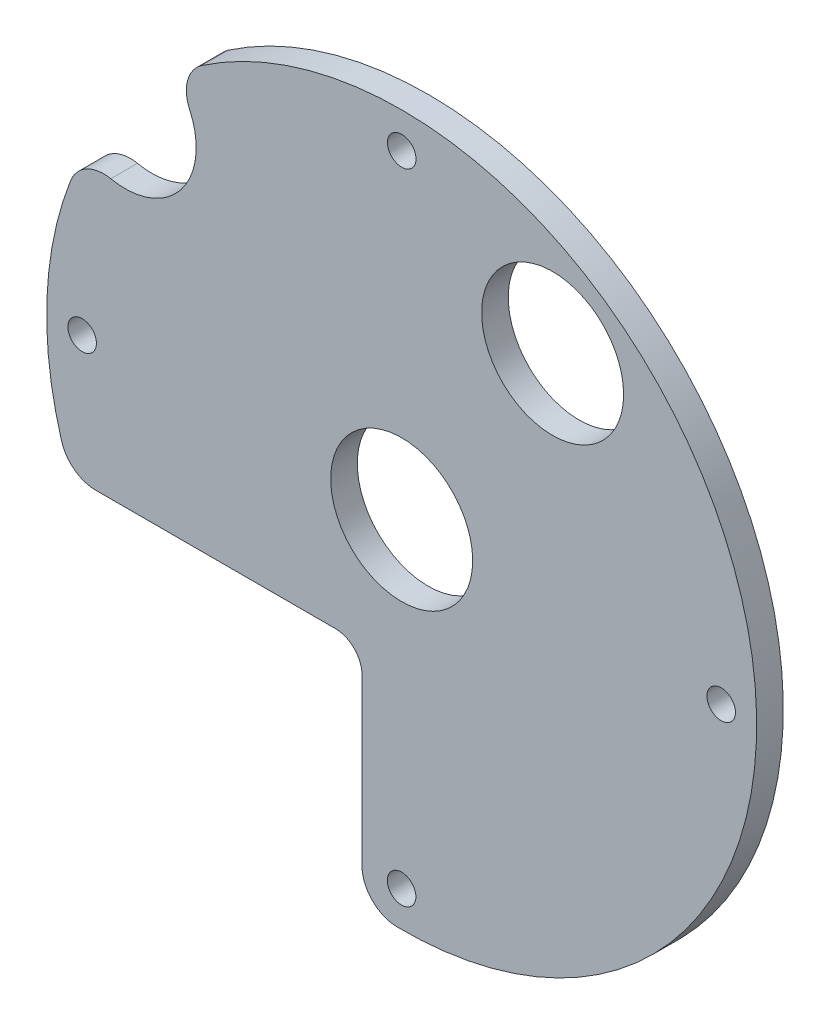
SolidWorks part; units mm, degrees
material "PET"
ref_plane "Front Plane" through (0, 0, 0) normal (0, 0, 1) x (1, 0, 0)
ref_plane "Top Plane" through (0, 0, 0) normal (0, 1, 0) x (1, 0, 0)
ref_plane "Right Plane" through (0, 0, 0) normal (1, 0, 0) x (0, 0, -1)
sketch "LayoutSke"
sketch_block_instance "Gearing 2.0-1"
sketch_block "Gearing 2.0" parameters "D5"=76.2, "D6"=25.4, "D7"=101.6, "D8"=19.05, "D1"=228.6, "D2"=123.2, "D3"=85.227, "D4"=76.454, "D9"=39.0329, "D10"=76.454, "D11"=47.625, "D12"=63.5
sketch "Sketch2" plane through (0, 0, 0) normal (0, 0, 1) x (1, 0, 0)
  line L1 (-114.3, 123.2) -> (114.3, 123.2)
  line L2 (-114.3, 123.2) -> (-114.3, -41.9)
  line L3 (-114.3, -41.9) -> (114.3, -41.9)
  line L4 (114.3, 123.2) -> (114.3, -41.9)
  dimension "D1" = 165.1
extrude "Boss-Extrude1" add sketch "Sketch2" along normal blind 4.7625
hole_wizard "1/2 (0.5) Diameter Hole1" positions "Sketch3" profile "Sketch4" hole size "1/2" standard "ANSI Inch" end condition through all
sketch "Sketch3" plane through (0, 0, 4.7625) normal (0, 0, 1) x (1, 0, 0)
  line L0 (114.3, 123.2) -> (-114.3, 123.2) construction
  point P0 (-38.227, 85.227)
  point P3 (38.227, 85.227)
  point P7 (11.2268, 45.984)
  dimension "D1" = 77.216
  dimension "D2" = 27.0002
sketch "Sketch4" plane through (-38.227, 85.227, 4.7625) normal (1, 0, 0) x (0, -1, 0)
  line L0 (0, 0) -> (0, 4.7625)
  line L1 (0, 4.7625) -> (12.7, 4.7625)
  line L2 (12.7, 4.7625) -> (12.7, 0)
  line L5 (12.7, 0) -> (0, 0)
  line L11 (0, -6.35) -> (0, 107.95) construction
  dimension "Thru Hole Dia." = 25.4
  dimension "Thru Hole Depth" = 4.7625
ref_axis "MotorShaft" through (-24.7438, -6.3341, 0) along (0, 0, 1)
ref_axis "IntermediateShaft" through (11.2395, 45.9865, 0) along (0, 0, 1)
sketch "Sketch5" plane through (0, 0, 4.7625) normal (0, 0, 1) x (1, 0, 0)
  line L0 (11.2395, 45.9865) -> (38.227, 85.227) construction
  line L10 (29.0606, 96.2614) -> (22.9081, 78.9046)
  line L11 (37.8038, 68.6601) -> (51.8105, 80.6153)
  line L12 (11.2395, 45.9865) -> (11.2395, -7.3535) construction
  arc A2 (29.0606, 96.2614) -> (51.8105, 80.6153) centre (11.2395, 45.9865) ccw
  circle A3 centre (11.2395, 45.9865) radius 50.8 construction
  arc A5 (37.8038, 68.6601) -> (22.9081, 78.9046) centre (11.2395, 45.9865) ccw
  dimension "D1" = 2.54
  dimension "D2" = 69.85
  dimension "D3" = 15
  dimension "D4" = 15
sketch "Sketch7" plane through (0, 0, 0) normal (0, 0, -1) x (-1, 0, 0)
  line L0 (-114.3, 123.2) -> (114.3, 123.2) construction
  line L1 (38.227, 85.227) -> (-38.227, 85.227) construction
  circle A0 centre (0, 180.35) radius 66.675
  point P4 (0, 123.2)
  point P6 (0, 113.675)
  dimension "D1" = 133.35
  dimension "D2" = 9.525
  dimension "D3" = 95.123
extrude "Cut-Extrude4" cut sketch "Sketch7" against normal through all
fillet "Fillet1" radius 6.35 4 edges at (-114.3, -41.9, 2.3813) (114.3, -41.9, 2.3813) (114.3, 123.2, 2.3813) (-114.3, 123.2, 2.3813)
sketch "Sketch8" plane through (0, 0, 4.7625) normal (0, 0, 1) x (1, 0, 0)
  line L0 (-107.95, -41.9) -> (107.95, -41.9) construction
  line L1 (-107.95, -41.9) -> (107.95, -41.9)
  line L2 (-114.3, -10.15) -> (-114.3, -35.55)
  line L3 (114.3, -35.55) -> (114.3, 116.85) construction
  line L4 (-53.975, -10.15) -> (-114.3, -10.15)
  line L6 (4.1275, 23.1875) -> (4.1275, -26.0533)
  line L7 (114.3, -10.15) -> (56.9451, -10.15)
  line L8 (-34.3429, 123.2) -> (-107.95, 123.2) construction
  line L9 (-114.3, 116.85) -> (-114.3, -35.55) construction
  line L10 (4.1275, 23.1875) -> (-53.975, 23.1875)
  line L11 (-53.975, 23.1875) -> (-53.975, -10.15)
  line L12 (114.3, -10.15) -> (114.3, -35.55)
  arc A0 (-114.3, -35.55) -> (-107.95, -41.9) centre (-107.95, -35.55) ccw construction
  arc A1 (-114.3, -35.55) -> (-107.95, -41.9) centre (-107.95, -35.55) ccw
  arc A2 (29.0606, 96.2614) -> (51.8105, 80.6153) centre (11.2395, 45.9865) ccw construction
  arc A3 (107.95, -41.9) -> (114.3, -35.55) centre (107.95, -35.55) ccw construction
  arc A4 (107.95, -41.9) -> (114.3, -35.55) centre (107.95, -35.55) ccw
  arc A6 (4.1275, -26.0533) -> (56.9451, -10.15) centre (11.2395, 45.9865) ccw
  dimension "D3" = 72.39
  dimension "D1" = 133.35
  dimension "D2" = 60.325
  dimension "D4" = 110.1725
  dimension "D5" = 100.0125
extrude "Cut-Extrude5" cut sketch "Sketch8" against normal through all
fillet "Fillet2" radius 4.7625 7 edges at (114.3, -10.15, 2.3813) (56.9451, -10.15, 2.3813) (4.1275, -26.0533, 2.3813) (4.1275, 23.1875, 2.3813) (-53.975, 23.1875, 2.3813) (-53.975, -10.15, 2.3813) (-114.3, -10.15, 2.3813)
sketch "Sketch9" plane through (0, 0, 4.7625) normal (0, 0, 1) x (1, 0, 0)
  circle A0 centre (-107.95, 116.85) radius 2.5527
  circle A1 centre (-109.5375, -5.3875) radius 2.5527
  circle A2 centre (109.5375, -5.3875) radius 2.5527
  circle A3 centre (107.95, 116.85) radius 2.5527
  dimension "D1" = 5.1054
extrude "Cut-Extrude6" cut sketch "Sketch9" against normal through all
sketch "Sketch10" plane through (0, 0, 4.7625) normal (0, 0, 1) x (1, 0, 0)
  circle A0 centre (11.2268, 45.984) radius 63.5
  dimension "D1" = 127
extrude "Cut-Extrude7" cut sketch "Sketch10" against normal through all flip side to cut
fillet "Fillet3" radius 6.35 4 edges at (4.1275, -17.1179, 2.3813) (-29.6411, 94.585, 2.3813) (-45.3893, 74.7393, 2.3813) (-48.0401, 23.1875, 2.3813)
sketch "Sketch11" plane through (0, 0, 4.7625) normal (0, 0, 1) x (1, 0, 0)
  line L0 (11.2395, 45.9865) -> (11.2395, 103.1365) construction
  circle A0 centre (11.2395, 103.1365) radius 2.5527
  dimension "D1" = 5.1054
  dimension "D2" = 57.15
extrude "Cut-Extrude8" cut sketch "Sketch11" against normal through all
pattern_circular "CirPattern1" count 4 over 360 about axis through (11.2268, 45.984, 4.7625) along (0, 0, 1) of "Cut-Extrude8"
